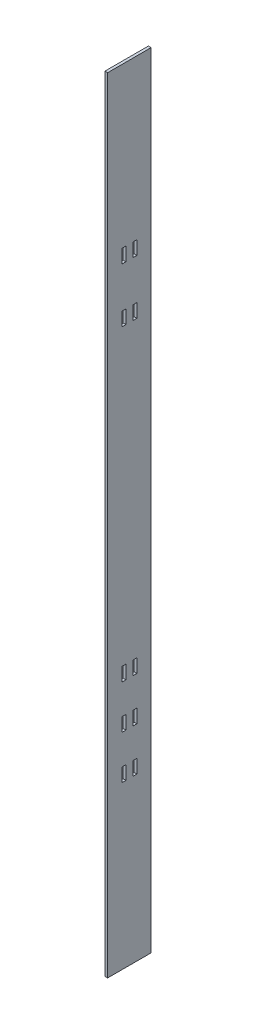
SolidWorks part; units mm, degrees
ref_plane "Front Plane" through (0, 0, 0) normal (0, 0, 1) x (1, 0, 0)
ref_plane "Top Plane" through (0, 0, 0) normal (0, 1, 0) x (1, 0, 0)
ref_plane "Right Plane" through (0, 0, 0) normal (1, 0, 0) x (0, 0, -1)
sketch "Sketch1" plane through (0, 0, 0) normal (1, 0, 0) x (0, 0, -1)
  line L1 (-25.4, 457.2) -> (25.4, 457.2)
  line L2 (-25.4, 457.2) -> (-25.4, -457.2)
  line L3 (-25.4, -457.2) -> (25.4, -457.2)
  line L4 (25.4, 457.2) -> (25.4, -457.2)
  line L5 (-25.4, 457.2) -> (25.4, -457.2) construction
  line L6 (-25.4, -457.2) -> (25.4, 457.2) construction
  point P0 (0, 0)
  dimension "D1" = 914.4
  dimension "D2" = 50.8
extrude "Boss-Extrude1" add sketch "Sketch1" along normal blind 3.175
sketch "Sketch2" plane through (3.175, 0, 0) normal (1, 0, 0) x (0, 0, -1)
  line L0 (-25.4, -457.2) -> (25.4, -457.2) construction
  line L1 (4, -201.6125) -> (8.7625, -201.6125)
  line L2 (4, -201.6125) -> (4, -217.4875)
  line L3 (4, -217.4875) -> (8.7625, -217.4875)
  line L4 (8.7625, -201.6125) -> (8.7625, -217.4875)
  line L5 (4, -201.6125) -> (8.7625, -217.4875) construction
  line L6 (4, -217.4875) -> (8.7625, -201.6125) construction
  point P0 (6.3813, -209.55)
  dimension "D1" = 4.7625
  dimension "D2" = 15.875
  dimension "D3" = 239.7125
  dimension "D4" = 4
extrude "Cut-Extrude1" cut sketch "Sketch2" against normal through all
mirror "Mirror1" about plane through (0, 0, 0) normal (0, 0, 1) of "Cut-Extrude1"
pattern_linear "LPattern1" count 2 spacing 50.8 along (0, 1, 0) count 2 spacing 50.8 along (0, -1, 0) of "Mirror1"
sketch "Sketch3" plane through (3.175, 0, 0) normal (1, 0, 0) x (0, 0, -1)
  line L0 (8.7625, -166.6875) -> (8.7625, -150.8125) construction
  line L1 (4, 207.9625) -> (8.7625, 207.9625)
  line L2 (4, 207.9625) -> (4, 192.0875)
  line L3 (4, 192.0875) -> (8.7625, 192.0875)
  line L4 (8.7625, 207.9625) -> (8.7625, 192.0875)
  line L5 (4, 207.9625) -> (8.7625, 192.0875) construction
  line L6 (4, 192.0875) -> (8.7625, 207.9625) construction
  line L7 (8.7625, -150.8125) -> (4, -150.8125) construction
  line L8 (4, -150.8125) -> (4, -166.6875) construction
  line L9 (0, 0) -> (0, 52.1648) construction
  line L10 (-4, 192.0875) -> (-8.7625, 207.9625) construction
  line L11 (-4, 207.9625) -> (-8.7625, 192.0875) construction
  line L12 (-8.7625, 207.9625) -> (-8.7625, 192.0875)
  line L13 (-4, 192.0875) -> (-8.7625, 192.0875)
  line L14 (-4, 207.9625) -> (-4, 192.0875)
  line L15 (-4, 207.9625) -> (-8.7625, 207.9625)
  point P0 (6.3812, 200.025)
  point P18 (-6.3812, 200.025)
  dimension "D1" = 342.9
extrude "Cut-Extrude2" cut sketch "Sketch3" against normal through all
pattern_linear "LPattern2" count 2 spacing 63.5 along (0, 1, 0) of "Cut-Extrude2"
